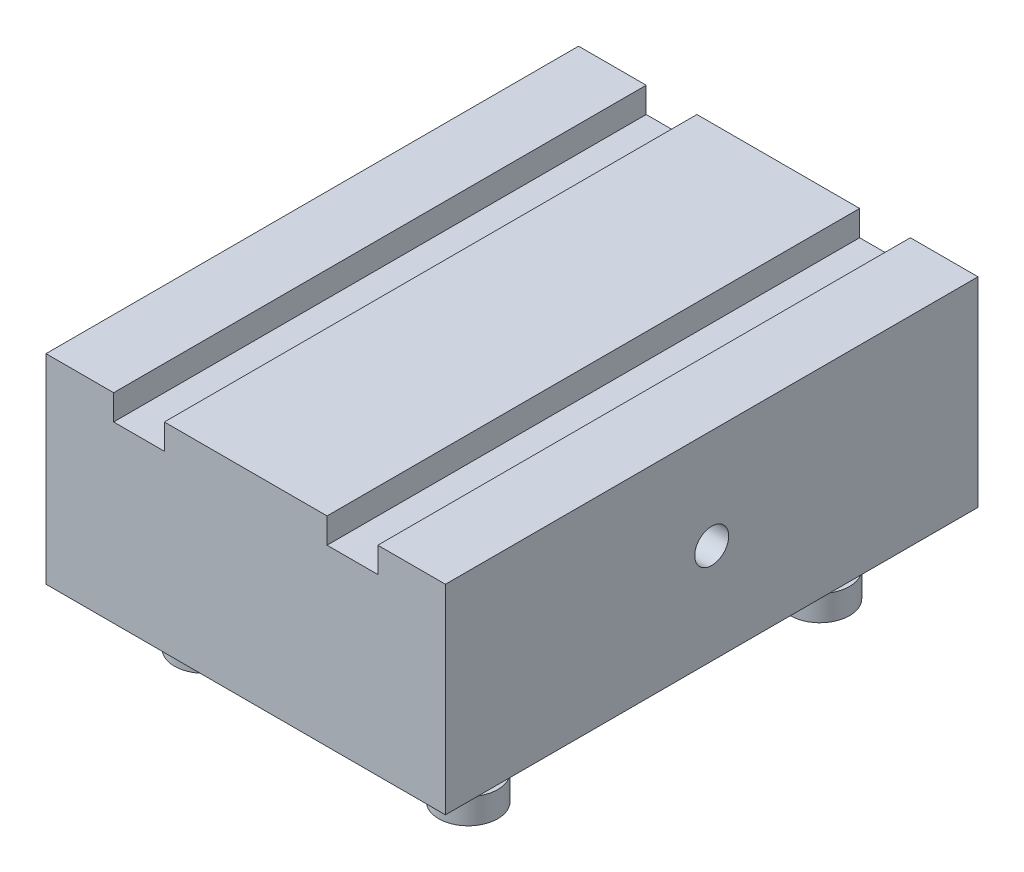
SolidWorks part; units mm, degrees
ref_plane "Front Plane" through (0, 0, 0) normal (0, 0, 1) x (1, 0, 0)
ref_plane "Top Plane" through (0, 0, 0) normal (0, 1, 0) x (1, 0, 0)
ref_plane "Right Plane" through (0, 0, 0) normal (1, 0, 0) x (0, 0, -1)
sketch "Sketch1" plane through (0, 0, 0) normal (0, 1, 0) x (1, 0, 0)
  line L1 (0, 0) -> (60, 0)
  line L2 (0, 0) -> (0, 80)
  line L3 (0, 80) -> (60, 80)
  line L4 (60, 0) -> (60, 80)
  dimension "D1" = 60
  dimension "D2" = 80
extrude "Boss-Extrude1" add sketch "Sketch1" against normal blind 30 contours L2 L3 L4 L1
sketch "Sketch2" plane through (0, 0, 0) normal (0, 0, 1) x (1, 0, 0)
  line L0 (0, 0) -> (60, 0) construction
  line L1 (10.16, 0) -> (10.16, -3.81)
  line L2 (10.16, -3.81) -> (13.97, -3.81)
  line L3 (13.97, -3.81) -> (17.78, -3.81)
  line L4 (17.78, -3.81) -> (17.78, 0)
  line L7 (30, 0) -> (30, -30) construction
  line L8 (0, -30) -> (60, -30) construction
  line L9 (42.22, -3.81) -> (42.22, 0)
  line L10 (46.03, -3.81) -> (42.22, -3.81)
  line L11 (49.84, -3.81) -> (46.03, -3.81)
  line L12 (49.84, 0) -> (49.84, -3.81)
  arc A0 (10.16, 0) -> (17.78, 0) centre (13.97, 0) ccw
  arc A1 (49.84, 0) -> (42.22, 0) centre (46.03, 0) cw
  line M4 (60, 0) -> (0, 0)
  dimension "D3" = 3.81
  dimension "D1" = 10.16
extrude "Cut-Extrude1" cut sketch "Sketch2" against normal through all contours A0 L1 L2 | A0 M4 | A0 L3 L4 | A1 M4 | L10 A1 L9 | L12 A1 L11 region at (11.011, -2.959, 0) region at (13.97, -1.617, 0) region at (46.03, -1.617, 0) region at (43.071, -2.959, 0) region at (16.929, -2.959, 0) region at (48.989, -2.959, 0)
sketch "Sketch3" plane through (0, -30, 0) normal (0, -1, 0) x (1, 0, 0)
  line L0 (60, -40) -> (0, -40) construction
  line L1 (60, 0) -> (60, -80) construction
  line L2 (0, 0) -> (0, -80) construction
  line L3 (49.84, -18.029) -> (49.84, -61.971) construction
  line L4 (30, 0) -> (30, -80) construction
  line L5 (0, 0) -> (60, 0) construction
  line L6 (0, -80) -> (60, -80) construction
  line L7 (10.16, -18.029) -> (10.16, -61.971) construction
  circle A0 centre (49.84, -13.584) radius 4.445
  circle A1 centre (10.16, -13.584) radius 4.445
  circle A2 centre (49.84, -66.416) radius 4.445
  circle A3 centre (10.16, -66.416) radius 4.445
  point P21 (49.84, -40)
  point P24 (10.16, -40)
  dimension "D2" = 10.16
  dimension "D3" = 8.89
  dimension "D1" = 21.971
extrude "Boss-Extrude2" add sketch "Sketch3" along normal blind 3.81
sketch "Sketch4" plane through (0, -33.81, 0) normal (0, -1, 0) x (1, 0, 0)
  line L0 (60, -40) -> (0, -40) construction
  line L1 (30, 0) -> (30, -80) construction
  line L2 (0, -80) -> (60, -80) construction
  circle A0 centre (49.84, -13.584) radius 2.54
  circle A2 centre (49.84, -13.584) radius 4.445 construction
  circle A3 centre (10.16, -13.584) radius 2.54
  circle A4 centre (10.16, -66.416) radius 2.54
  circle A5 centre (49.84, -66.416) radius 2.54
  dimension "D1" = 5.08
extrude "Boss-Extrude3" add sketch "Sketch4" along normal blind 2.54
sketch "Sketch5" plane through (0, -36.35, 0) normal (0, -1, 0) x (1, 0, 0)
  line L0 (30, 0) -> (30, -80) construction
  line L1 (0, -40) -> (60, -40) construction
  circle A0 centre (10.16, -13.584) radius 4.445
  circle A1 centre (10.16, -13.584) radius 4.445 construction
  circle A2 centre (10.16, -66.416) radius 4.445
  circle A3 centre (49.84, -66.416) radius 4.445
  circle A4 centre (49.84, -13.584) radius 4.445
extrude "Boss-Extrude4" add sketch "Sketch5" along normal blind 3.81
sketch "Sketch6" plane through (60, 0, 0) normal (1, 0, 0) x (0, 0, -1)
  line L0 (40, 0) -> (40, -30) construction
  line L1 (0, 0) -> (80, 0) construction
  line L2 (0, -30) -> (80, -30) construction
  line L3 (0, -15) -> (80, -15) construction
  line L4 (0, -30) -> (0, 0) construction
  line L5 (80, -30) -> (80, 0) construction
  point P12 (40, -15)
hole_wizard "1/4-20 Tapped Hole1" positions "Sketch13" profile "Sketch14" tap size "1/4-20" standard "ANSI Inch" end condition through all
sketch "Sketch13" plane through (60, 0, 0) normal (1, 0, 0) x (0, 0, -1)
  point P0 (40, -15)
sketch "Sketch14" plane through (60, -15, -40) normal (0, 1, 0) x (0, 0, -1)
  line L0 (0, 0) -> (0, 60)
  line L1 (0, 60) -> (2.5527, 60)
  line L2 (2.5527, 60) -> (2.5527, 0)
  line L5 (2.5527, 0) -> (0, 0)
  line L11 (0, -6.35) -> (0, 107.95) construction
  dimension "Thru Tap Drill Dia." = 5.1054
  dimension "Thru Tap Drill Depth" = 60
cosmetic thread "Hole Thread3" parameters "D2"=6.35
